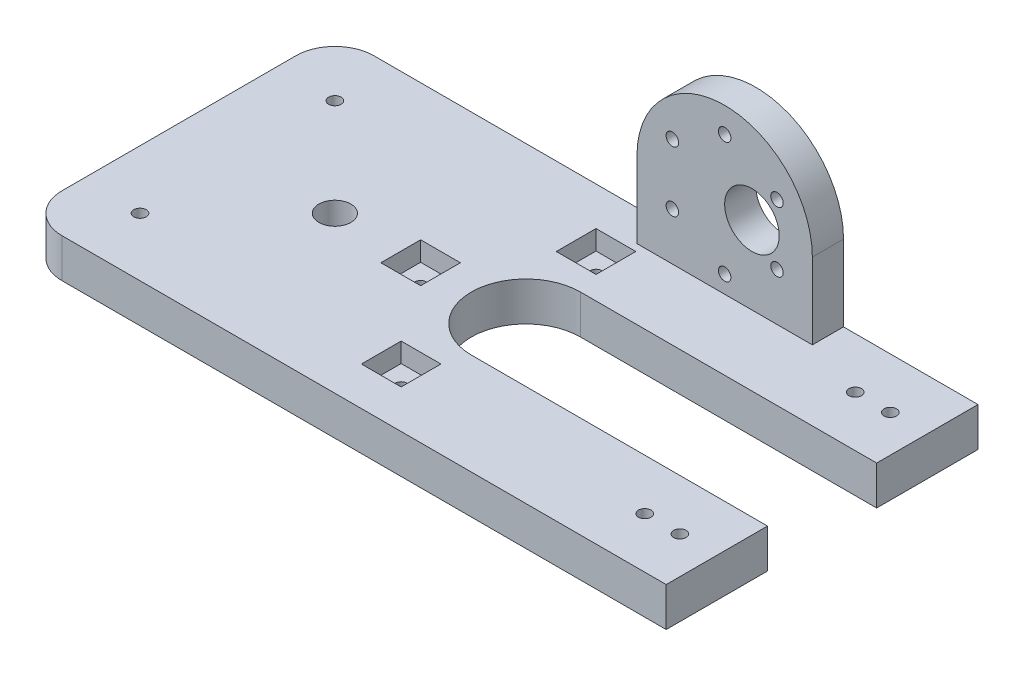
SolidWorks part; units mm, degrees
ref_plane "正面" through (0, 0, 0) normal (0, 0, 1) x (1, 0, 0)
ref_plane "平面" through (0, 0, 0) normal (0, 1, 0) x (1, 0, 0)
ref_plane "右側面" through (0, 0, 0) normal (1, 0, 0) x (0, 0, -1)
sketch "ｽｹｯﾁ1" plane through (0, 0, 0) normal (0, 1, 0) x (1, 0, 0)
  line L0 (82.5, 14) -> (82.5, 40)
  line L1 (-82.5, -40) -> (82.5, -40)
  line L2 (-82.5, -40) -> (-82.5, 40)
  line L3 (-82.5, 40) -> (82.5, 40)
  line L4 (82.5, -40) -> (82.5, -14)
  line L5 (-82.5, -40) -> (82.5, 40) construction
  line L6 (-82.5, 40) -> (82.5, -40) construction
  line L7 (82.5, 14) -> (-7.5, 14)
  line L9 (82.5, -14) -> (-7.5, -14)
  line L10 (-7.5, 14) -> (-7.5, -14)
  line L11 (-82.5, 40) -> (35272.8391, -35315.3391) construction
  line L12 (-82.5, -40) -> (35272.8391, 35315.3391) construction
  circle A0 centre (-42.5, 0) radius 4.1
  point P0 (0, 0)
  point P17 (-42.5, 0)
  dimension "D5" = 8.2
  dimension "D1" = 80
  dimension "D2" = 75
  dimension "D3" = 28
  dimension "D4" = 90
  dimension "D6" = 45
  dimension "D7" = 45
extrude "ﾎﾞｽ - 押し出し1" add sketch "ｽｹｯﾁ1" along normal blind 10
sketch "ｽｹｯﾁ2" plane through (0, 10, 0) normal (0, 1, 0) x (1, 0, 0)
  line L2 (-82.5, 40) -> (-2.5, -40) construction
  line L4 (82.5, 40) -> (-82.5, 40) construction
  circle A0 centre (-67.5, 25) radius 1.6
  circle A3 centre (-67.5, -25) radius 1.6
  dimension "D1" = 3.2
  dimension "D3" = 50
  dimension "D4" = 25
  dimension "D5" = 45
fillet "ﾌｨﾚｯﾄ1" radius 10 2 edges at (-82.5, 5, -40) (-82.5, 5, 40)
fillet "ﾌｨﾚｯﾄ2" 2 edges at (-7.5, 5, 14) (-7.5, 5, -14) type full round first side face at (37.5, 5, 14) second side face at (37.5, 5, -14) middle face at (-7.5, 5, 0)
sketch "ｽｹｯﾁ5" plane through (0, 10, 0) normal (0, 1, 0) x (1, 0, 0)
  line L0 (82.5, 40) -> (-72.5, 40) construction
  line L1 (48, 32) -> (3, 32)
  line L2 (48, 32) -> (48, 40)
  line L3 (48, 40) -> (3, 40)
  line L4 (3, 32) -> (3, 40)
  line L5 (3, 40) -> (48, 32) construction
  line L7 (3, 32) -> (48, 40) construction
  arc A1 (6.5, 14) -> (6.5, -14) centre (6.5, 0) ccw construction
  point P4 (25.5, 36)
  dimension "D1" = 19
  dimension "D2" = 45
  dimension "D3" = 8
extrude "ﾎﾞｽ - 押し出し4" add sketch "ｽｹｯﾁ5" along normal blind 42
fillet "ﾌｨﾚｯﾄ3" 2 edges at (48, 52, -36) (3, 52, -36) type full round first side face at (48, 31, -36) second side face at (3, 31, -36) middle face at (25.5, 52, -36)
sketch "ｽｹｯﾁ6" plane through (0, 0, -32) normal (0, 0, 1) x (1, 0, 0)
  line L0 (-38.4, 10) -> (-46.6, 10) construction
  circle A0 centre (32.5, 30) radius 7
  circle A2 centre (25.5, 45.5) radius 1.6
  circle A3 centre (25.5, 30) radius 15.5 construction
  circle A5 centre (38.9234, 37.75) radius 1.6
  circle A6 centre (38.9234, 22.25) radius 1.6
  circle A7 centre (25.5, 14.5) radius 1.6
  circle A8 centre (12.0766, 22.25) radius 1.6
  circle A9 centre (12.0766, 37.75) radius 1.6
  point P21 (25.5, 30)
  dimension "D2" = 14
  dimension "D3" = 6
  dimension "D5" = 31
  dimension "D1" = 3.2
  dimension "D4" = 20
  dimension "D6" = 7
  dimension "D7" = 70.9
extrude "ｶｯﾄ - 押し出し1" cut sketch "ｽｹｯﾁ6" against normal through all
sketch "ｽｹｯﾁ7" plane through (0, 10, 0) normal (0, 1, 0) x (1, 0, 0)
  line L1 (-5.6, 30.1) -> (4.6, 30.1)
  line L2 (-5.6, 30.1) -> (-5.6, 19.9)
  line L3 (-5.6, 19.9) -> (4.6, 19.9)
  line L4 (4.6, 30.1) -> (4.6, 19.9)
  line L5 (-5.6, 30.1) -> (4.6, 19.9) construction
  line L6 (-5.6, 19.9) -> (4.6, 30.1) construction
  line L7 (-5.6, -19.9) -> (4.6, -19.9)
  line L8 (-5.6, -19.9) -> (-5.6, -30.1)
  line L9 (-5.6, -30.1) -> (4.6, -30.1)
  line L10 (4.6, -19.9) -> (4.6, -30.1)
  line L11 (-5.6, -19.9) -> (4.6, -30.1) construction
  line L12 (-5.6, -30.1) -> (4.6, -19.9) construction
  line L13 (-25.6, -5.1) -> (-15.4, -5.1)
  line L14 (-25.6, -5.1) -> (-25.6, 5.1)
  line L15 (-25.6, 5.1) -> (-15.4, 5.1)
  line L16 (-15.4, -5.1) -> (-15.4, 5.1)
  line L17 (-25.6, -5.1) -> (-15.4, 5.1) construction
  line L18 (-25.6, 5.1) -> (-15.4, -5.1) construction
  circle A0 centre (-42.5, 0) radius 4.1 construction
  point P0 (-0.5, 25)
  point P4 (-0.5, -25)
  point P12 (-20.5, 0)
  dimension "D1" = 10.2
  dimension "D4" = 42
  dimension "D2" = 25
  dimension "D3" = 25
  dimension "D5" = 20
extrude "ｶｯﾄ - 押し出し2" cut sketch "ｽｹｯﾁ7" against normal blind 5
sketch "ｽｹｯﾁ8" plane through (0, 10, 0) normal (0, 1, 0) x (1, 0, 0)
  line L0 (82.5, 14) -> (82.5, 40) construction
  line L1 (82.5, -40) -> (82.5, -14) construction
  circle A0 centre (73, 27) radius 1.6
  circle A1 centre (64, 27) radius 1.6
  circle A2 centre (64, -27) radius 1.6
  circle A3 centre (73, -27) radius 1.6
  point P8 (82.5, 27)
  point P14 (82.5, -27)
  dimension "D3" = 3.2
  dimension "D4" = 9.5
  dimension "D1" = 9.5
  dimension "D2" = 9
  dimension "D5" = 9
extrude "ｶｯﾄ - 押し出し3" cut sketch "ｽｹｯﾁ8" against normal through all
extrude "ｶｯﾄ - 押し出し5" cut sketch "ｽｹｯﾁ2" against normal through all
sketch "ｽｹｯﾁ9" plane through (0, 0, 0) normal (0, 1, 0) x (1, 0, 0)
  line L0 (-5.6, 30.1) -> (4.6, 19.9) construction
  line L1 (-5.6, 19.9) -> (4.6, 30.1) construction
  line L2 (-5.6, -19.9) -> (4.6, -30.1) construction
  line L3 (-5.6, -30.1) -> (4.6, -19.9) construction
  line L4 (-25.6, 5.1) -> (-15.4, -5.1) construction
  line L5 (-25.6, -5.1) -> (-15.4, 5.1) construction
  circle A0 centre (-0.5, 25) radius 1.5
  circle A1 centre (-20.5, 0) radius 1.5
  circle A2 centre (-0.5, -25) radius 1.5
  point P30 (0, 0)
  point P31 (-20.5, 0)
  point P32 (0, 0)
  point P33 (-0.5, 25)
  point P34 (0, 0)
  point P35 (-0.5, -25)
  dimension "D1" = 3
extrude "ｶｯﾄ - 押し出し6" cut sketch "ｽｹｯﾁ9" along normal up to next
sketch "ｽｹｯﾁ10" plane through (0, 0, 0) normal (0, -1, 0) x (1, 0, 0)
  line L1 (-67.5, 28.1) -> (-70.1847, 26.55)
  line L2 (-70.1847, 26.55) -> (-70.1847, 23.45)
  line L3 (-70.1847, 23.45) -> (-67.5, 21.9)
  line L4 (-67.5, 21.9) -> (-64.8153, 23.45)
  line L5 (-64.8153, 23.45) -> (-64.8153, 26.55)
  line L6 (-64.8153, 26.55) -> (-67.5, 28.1)
  line L7 (-67.5, -21.9) -> (-70.1847, -23.45)
  line L8 (-70.1847, -23.45) -> (-70.1847, -26.55)
  line L9 (-70.1847, -26.55) -> (-67.5, -28.1)
  line L10 (-67.5, -28.1) -> (-64.8153, -26.55)
  line L11 (-64.8153, -26.55) -> (-64.8153, -23.45)
  line L12 (-64.8153, -23.45) -> (-67.5, -21.9)
  circle A0 centre (-67.5, 25) radius 2.6847 construction
  circle A1 centre (-67.5, -25) radius 2.6847 construction
  circle A2 centre (-0.5, 25) radius 3
  circle A3 centre (-20.5, 0) radius 3
  circle A4 centre (-0.5, -25) radius 3
  dimension "D3" = 6
  dimension "D1" = 3.1
  dimension "D2" = 3.1
extrude "ｶｯﾄ - 押し出し7" cut sketch "ｽｹｯﾁ10" against normal blind 2
